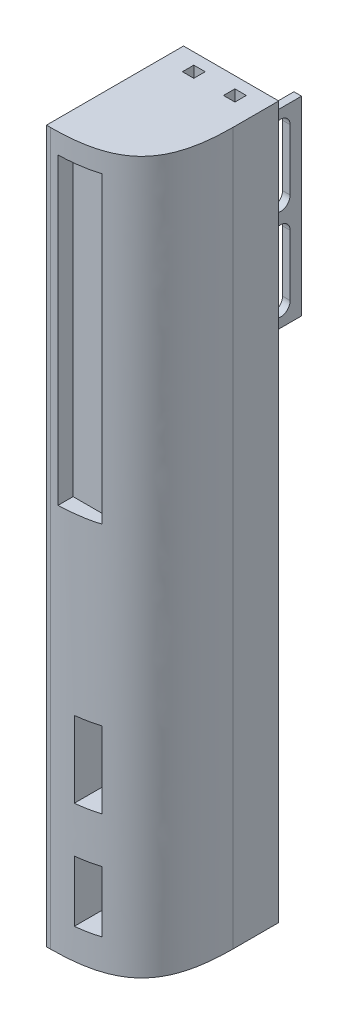
SolidWorks part; units mm, degrees
ref_plane "Front Plane" through (0, 0, 0) normal (0, 0, 1) x (1, 0, 0)
ref_plane "Top Plane" through (0, 0, 0) normal (0, 1, 0) x (1, 0, 0)
ref_plane "Right Plane" through (0, 0, 0) normal (1, 0, 0) x (0, 0, -1)
sketch "Sketch1" plane through (0, 0, 0) normal (0, 1, 0) x (1, 0, 0)
  line L1 (0, 0) -> (25, 0)
  line L2 (0, 0) -> (0, 36)
  line L3 (0, 36) -> (25, 36)
  line L4 (25, 0) -> (25, 36)
  dimension "D1" = 36
  dimension "D2" = 25
extrude "Boss-Extrude1" add sketch "Sketch1" along normal blind 186.9
fillet "Fillet1" radius 24 1 edges at (25, 93.45, 0) conic rho 0.55
sketch "Sketch2" plane through (0, 0, 0) normal (-1, 0, 0) x (0, 0, 1)
  line L0 (-24, 0) -> (0, 0) construction
  line L1 (-6.2, 83.2) -> (-1.2, 83.2)
  line L2 (-6.2, 83.2) -> (-6.2, 73.2)
  line L3 (-6.2, 73.2) -> (-1.2, 73.2)
  line L4 (-1.2, 83.2) -> (-1.2, 73.2)
  line L5 (0, 186.9) -> (0, 0) construction
  dimension "D1" = 73.2
  dimension "D2" = 1.2
  dimension "D3" = 5
  dimension "D4" = 10
extrude "Cut-Extrude1" cut sketch "Sketch2" against normal blind 4
sketch "Sketch3" plane through (0, 0, 0) normal (-1, 0, 0) x (0, 0, 1)
  line L1 (-14, 33.2) -> (-6, 33.2)
  line L2 (-14, 33.2) -> (-14, 28)
  line L3 (-14, 28) -> (-6, 28)
  line L4 (-6, 33.2) -> (-6, 28)
  line L5 (-36, 0) -> (0, 0) construction
  line L6 (0, 186.9) -> (0, 0) construction
  line L8 (-22, 33.2) -> (-30, 33.2)
  line L9 (-22, 33.2) -> (-22, 28)
  line L10 (-22, 28) -> (-30, 28)
  line L11 (-30, 33.2) -> (-30, 28)
  line L12 (-6, 61.2) -> (-14, 61.2)
  line L13 (-6, 61.2) -> (-6, 66.8)
  line L14 (-6, 66.8) -> (-14, 66.8)
  line L15 (-14, 61.2) -> (-14, 66.8)
  line L16 (-22, 66.8) -> (-30, 66.8)
  line L17 (-22, 66.8) -> (-22, 61.2)
  line L18 (-22, 61.2) -> (-30, 61.2)
  line L19 (-30, 66.8) -> (-30, 61.2)
  dimension "D1" = 28
  dimension "D2" = 6
  dimension "D3" = 8
  dimension "D4" = 5.2
  dimension "D5" = 8
  dimension "D6" = 8
  dimension "D7" = 28
  dimension "D8" = 5.6
  dimension "D9" = 8
  dimension "D10" = 6
  dimension "D11" = 8
  dimension "D12" = 5.6
  dimension "D13" = 8
extrude "Cut-Extrude2" cut sketch "Sketch3" against normal blind 10
sketch "Sketch4" plane through (0, 0, 0) normal (-1, 0, 0) x (0, 0, 1)
  line L0 (-36, 0) -> (0, 0) construction
  line L1 (-26, 160) -> (-67, 160)
  line L2 (-26, 160) -> (-26, 110)
  line L3 (-26, 110) -> (-67, 110)
  line L4 (-67, 160) -> (-67, 110)
  line L5 (-36, 186.9) -> (-36, 0) construction
  dimension "D1" = 160
  dimension "D2" = 10
  dimension "D3" = 31
  dimension "D4" = 110
extrude "Boss-Extrude2" add sketch "Sketch4" along normal blind 2
sketch "Sketch5" plane through (-2, 0, 0) normal (-1, 0, 0) x (0, 0, 1)
  line L0 (-67, 110) -> (-26, 110) construction
  line L1 (-67, 160) -> (-67, 110) construction
  line L4 (-59, 131) -> (-59, 115)
  line L6 (-64, 131) -> (-64, 115)
  line L7 (-26, 160) -> (-67, 160) construction
  line L9 (-64, 139) -> (-64, 155)
  line L11 (-59, 139) -> (-59, 155)
  arc A0 (-64, 115) -> (-59, 115) centre (-61.5, 115) ccw
  arc A2 (-59, 131) -> (-64, 131) centre (-61.5, 131) ccw
  arc A3 (-59, 155) -> (-64, 155) centre (-61.5, 155) ccw
  arc A4 (-64, 139) -> (-59, 139) centre (-61.5, 139) ccw
  dimension "D1" = 5
  dimension "D4" = 16
  dimension "D5" = 16
  dimension "D2" = 5
  dimension "D3" = 5.5
  dimension "D6" = 5
extrude "Cut-Extrude3" cut sketch "Sketch5" against normal up to next
chamfer "Chamfer1" distance 16 angle 45 1 edges at (0, 135, -36)
sketch "Sketch6" plane through (0, 0, -36) normal (0, 0, -1) x (-1, 0, 0)
  line L0 (-25, 186.9) -> (-25, 0) construction
  line L1 (-21, 182.9) -> (-15, 182.9)
  line L2 (-21, 182.9) -> (-21, 178.9)
  line L3 (-21, 178.9) -> (-15, 178.9)
  line L4 (-15, 182.9) -> (-15, 178.9)
  line L5 (-25, 186.9) -> (0, 186.9) construction
  line L6 (-1, 186.9) -> (-25, 186.9) construction
  line L7 (-10.2, 182.9) -> (-4.2, 182.9)
  line L8 (-10.2, 182.9) -> (-10.2, 178.9)
  line L9 (-10.2, 178.9) -> (-4.2, 178.9)
  line L10 (-4.2, 182.9) -> (-4.2, 178.9)
  dimension "D1" = 4
  dimension "D2" = 4
  dimension "D3" = 4
  dimension "D4" = 6
  dimension "D5" = 6
  dimension "D6" = 4.8
  dimension "D7" = 4
extrude "Cut-Extrude4" cut sketch "Sketch6" against normal blind 9
sketch "Sketch7" plane through (0, 186.9, 0) normal (0, 1, 0) x (1, 0, 0)
  line L0 (25, 24) -> (25, 36) construction
  line L1 (19.5, 33) -> (16.5, 33)
  line L2 (19.5, 33) -> (19.5, 30)
  line L3 (19.5, 30) -> (16.5, 30)
  line L4 (16.5, 33) -> (16.5, 30)
  line L5 (25, 36) -> (0, 36) construction
  line L7 (8.7, 33) -> (5.7, 33)
  line L8 (8.7, 33) -> (8.7, 30)
  line L9 (8.7, 30) -> (5.7, 30)
  line L10 (5.7, 33) -> (5.7, 30)
  dimension "D1" = 5.5
  dimension "D2" = 3
  dimension "D3" = 3
  dimension "D4" = 3
  dimension "D5" = 3
  dimension "D6" = 3
  dimension "D7" = 3
  dimension "D8" = 7.8
extrude "Cut-Extrude5" cut sketch "Sketch7" against normal blind 10
sketch "Sketch8" plane through (0, 0, 0) normal (0, -1, 0) x (1, 0, 0)
  line L0 (25, -36) -> (0, -36) construction
  line L1 (3, -5) -> (7, -5)
  line L2 (3, -5) -> (3, -33)
  line L3 (3, -33) -> (7, -33)
  line L4 (7, -5) -> (7, -29)
  line L5 (0, -36) -> (0, 0) construction
  line L6 (25, -24) -> (25, -36) construction
  line L7 (7, -33) -> (21, -33)
  line L9 (7, -29) -> (21, -29)
  line L10 (21, -33) -> (21, -29)
  dimension "D1" = 5
  dimension "D2" = 3
  dimension "D3" = 3
  dimension "D4" = 4
  dimension "D5" = 4
  dimension "D6" = 4
  dimension "D7" = 14
  dimension "D8" = 28
extrude "Boss-Extrude3" add sketch "Sketch8" along normal blind 4
sketch "Sketch9" plane through (0, 0, 0) normal (0, -1, 0) x (1, 0, 0)
  line L0 (21, -29) -> (7, -29) construction
  line L1 (7, -29) -> (7, -5) construction
  circle A0 centre (14, -22) radius 2
  dimension "D1" = 4
  dimension "D2" = 7
  dimension "D3" = 7
extrude "Cut-Extrude6" cut sketch "Sketch9" against normal blind 5
sketch "Sketch10" plane through (0, 0, 0) normal (0, -1, 0) x (1, 0, 0)
  line L0 (7, -29) -> (7, -5) construction
  circle A0 centre (14, -12) radius 1.5
  circle A1 centre (14, -22) radius 2 construction
  dimension "D1" = 7
  dimension "D2" = 10
  dimension "D3" = 3
extrude "Cut-Extrude7" cut sketch "Sketch10" against normal blind 4
sketch "Sketch11" plane through (0, 0, 0) normal (0, 0, 1) x (1, 0, 0)
  line L0 (0, 186.9) -> (0, 0) construction
  line L1 (7, 24) -> (13, 24)
  line L2 (7, 24) -> (7, 8)
  line L3 (7, 8) -> (13, 8)
  line L4 (13, 24) -> (13, 8)
  line L5 (0, 0) -> (1, 0) construction
  line L7 (7, 36) -> (13, 36)
  line L8 (7, 36) -> (7, 56)
  line L9 (7, 56) -> (13, 56)
  line L10 (13, 36) -> (13, 56)
  dimension "D1" = 7
  dimension "D2" = 8
  dimension "D3" = 16
  dimension "D4" = 6
  dimension "D5" = 12
  dimension "D6" = 6
  dimension "D7" = 20
  dimension "D8" = 7
extrude "Cut-Extrude8" cut sketch "Sketch11" against normal blind 8
sketch "Sketch12" plane through (0, 0, 0) normal (0, 0, 1) x (1, 0, 0)
  line L0 (0, 186.9) -> (0, 0) construction
  line L1 (3, 181.6) -> (13, 181.6)
  line L2 (3, 181.6) -> (3, 101.9)
  line L3 (3, 101.9) -> (13, 101.9)
  line L4 (13, 181.6) -> (13, 101.9)
  line L5 (25, 186.9) -> (1, 186.9) construction
  dimension "D1" = 3
  dimension "D2" = 5.3
  dimension "D3" = 10
  dimension "D4" = 79.7
extrude "Cut-Extrude9" cut sketch "Sketch12" against normal blind 4
